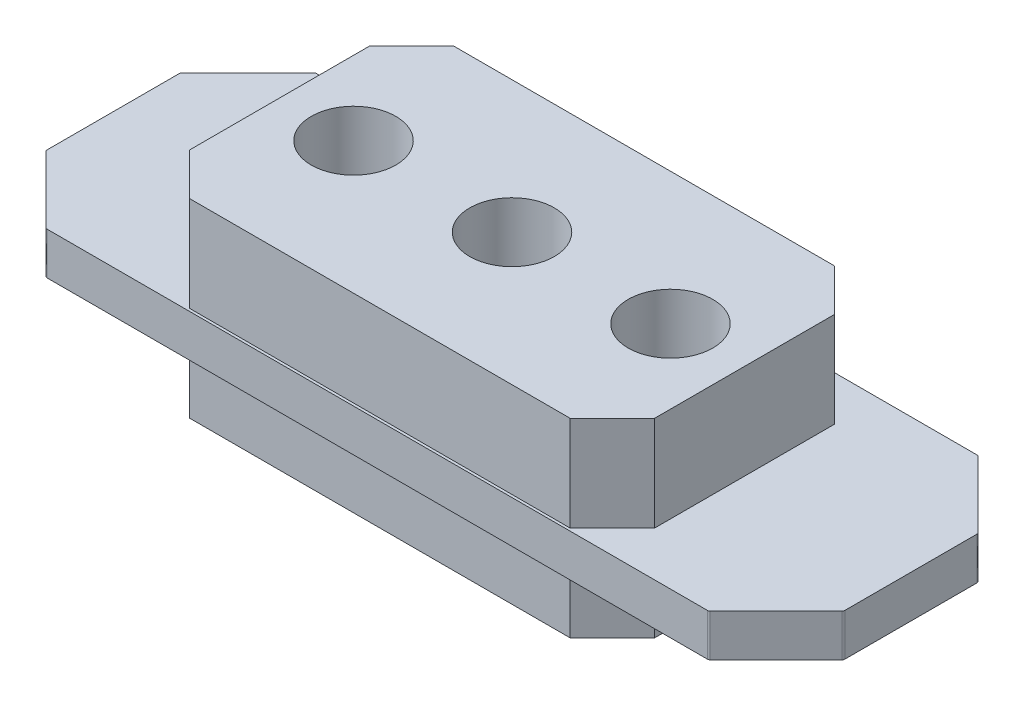
SolidWorks part; units mm, degrees
ref_plane "Front" through (0, 0, 0) normal (0, 0, 1) x (1, 0, 0)
ref_plane "Top" through (0, 0, 0) normal (0, 1, 0) x (1, 0, 0)
ref_plane "Right" through (0, 0, 0) normal (1, 0, 0) x (0, 0, -1)
sketch "Sketch1" plane through (0, 0, 0) normal (0, 1, 0) x (1, 0, 0)
  line L0 (9.5, 1.5) -> (9.5, -1.5) construction
  line L7 (10, -2) -> (14, -2) construction
  line L8 (14.5, -1.5) -> (14.5, 1.5) construction
  line L9 (14, 2) -> (10, 2) construction
  line L10 (9.5, 1.5) -> (9.5, -1.5) construction
  line L11 (10, -2) -> (14, -2) construction
  line L12 (14.5, -1.5) -> (14.5, 1.5) construction
  line L13 (14, 2) -> (10, 2) construction
  line L14 (-15.1, 2.5) -> (-15.1, -2.5)
  line L15 (-15.071, -2.571) -> (-12.571, -5.071)
  line L16 (-12.5, -5.1) -> (12.5, -5.1)
  line L17 (12.571, -5.071) -> (15.071, -2.571)
  line L18 (15.1, -2.5) -> (15.1, 2.5)
  line L19 (15.071, 2.571) -> (12.571, 5.071)
  line L20 (12.5, 5.1) -> (-12.5, 5.1)
  line L21 (-12.571, 5.071) -> (-15.071, 2.571)
  line L22 (-15.1, 2.5) -> (-15.1, -2.5)
  line L23 (-15.071, -2.571) -> (-12.571, -5.071)
  line L24 (-12.5, -5.1) -> (12.5, -5.1)
  line L25 (12.571, -5.071) -> (15.071, -2.571)
  line L26 (15.1, -2.5) -> (15.1, 2.5)
  line L27 (15.071, 2.571) -> (12.571, 5.071)
  line L28 (12.5, 5.1) -> (-12.5, 5.1)
  line L29 (-12.571, 5.071) -> (-15.071, 2.571)
  line L30 (-10, 2) -> (-14, 2) construction
  line L31 (-14.5, 1.5) -> (-14.5, -1.5) construction
  line L32 (-14, -2) -> (-10, -2) construction
  line L33 (-9.5, -1.5) -> (-9.5, 1.5) construction
  line L34 (-10, 2) -> (-14, 2) construction
  line L35 (-14.5, 1.5) -> (-14.5, -1.5) construction
  line L36 (-14, -2) -> (-10, -2) construction
  line L37 (-9.5, -1.5) -> (-9.5, 1.5) construction
  circle A0 centre (-6, 0) radius 1 construction
  circle A1 centre (6, 0) radius 1 construction
  circle A2 centre (0, 0) radius 1 construction
  circle A3 centre (-6, 0) radius 1
  circle A4 centre (6, 0) radius 1
  circle A5 centre (0, 0) radius 1
  arc A6 (9.5, -1.5) -> (10, -2) centre (10, -1.5) ccw construction
  arc A7 (14, -2) -> (14.5, -1.5) centre (14, -1.5) ccw construction
  arc A8 (-15.071, 2.571) -> (-15.1, 2.5) centre (-15.0029, 2.5018) ccw
  arc A9 (-15.1, -2.5) -> (-15.071, -2.571) centre (-15.0029, -2.5018) ccw
  arc A10 (-12.571, -5.071) -> (-12.5, -5.1) centre (-12.5018, -5.0029) ccw
  arc A11 (12.5, -5.1) -> (12.571, -5.071) centre (12.5018, -5.0029) ccw
  arc A12 (15.071, -2.571) -> (15.1, -2.5) centre (15.0029, -2.5018) ccw
  arc A13 (15.1, 2.5) -> (15.071, 2.571) centre (15.0029, 2.5018) ccw
  arc A14 (12.571, 5.071) -> (12.5, 5.1) centre (12.5018, 5.0029) ccw
  arc A15 (-12.5, 5.1) -> (-12.571, 5.071) centre (-12.5018, 5.0029) ccw
  arc A16 (-15.071, 2.571) -> (-15.1, 2.5) centre (-15.0029, 2.5018) ccw
  arc A17 (-15.1, -2.5) -> (-15.071, -2.571) centre (-15.0029, -2.5018) ccw
  arc A18 (-12.571, -5.071) -> (-12.5, -5.1) centre (-12.5018, -5.0029) ccw
  arc A19 (12.5, -5.1) -> (12.571, -5.071) centre (12.5018, -5.0029) ccw
  arc A20 (15.071, -2.571) -> (15.1, -2.5) centre (15.0029, -2.5018) ccw
  arc A21 (15.1, 2.5) -> (15.071, 2.571) centre (15.0029, 2.5018) ccw
  arc A22 (12.571, 5.071) -> (12.5, 5.1) centre (12.5018, 5.0029) ccw
  arc A23 (-12.5, 5.1) -> (-12.571, 5.071) centre (-12.5018, 5.0029) ccw
  arc A24 (14.5, 1.5) -> (14, 2) centre (14, 1.5) ccw construction
  arc A25 (10, 2) -> (9.5, 1.5) centre (10, 1.5) ccw construction
  arc A26 (9.5, -1.5) -> (10, -2) centre (10, -1.5) ccw construction
  arc A27 (14, -2) -> (14.5, -1.5) centre (14, -1.5) ccw construction
  arc A28 (14.5, 1.5) -> (14, 2) centre (14, 1.5) ccw construction
  arc A29 (10, 2) -> (9.5, 1.5) centre (10, 1.5) ccw construction
  arc A30 (-14, 2) -> (-14.5, 1.5) centre (-14, 1.5) ccw construction
  arc A31 (-14.5, -1.5) -> (-14, -2) centre (-14, -1.5) ccw construction
  arc A32 (-10, -2) -> (-9.5, -1.5) centre (-10, -1.5) ccw construction
  arc A33 (-9.5, 1.5) -> (-10, 2) centre (-10, 1.5) ccw construction
  arc A34 (-14, 2) -> (-14.5, 1.5) centre (-14, 1.5) ccw construction
  arc A35 (-14.5, -1.5) -> (-14, -2) centre (-14, -1.5) ccw construction
  arc A36 (-10, -2) -> (-9.5, -1.5) centre (-10, -1.5) ccw construction
  arc A37 (-9.5, 1.5) -> (-10, 2) centre (-10, 1.5) ccw construction
  point P0 (0, 0)
  dimension "D1" = 0
extrude "Boss-Extrude3" add sketch "Sketch1" along normal blind 1.6
sketch "Sketch3" plane through (0, 1.6, 0) normal (0, 1, 0) x (1, 0, 0)
  line L0 (-8.8, 5) -> (-8.8, -5)
  line L1 (8.8, 5) -> (8.8, -5)
  line L2 (-8.8, 5) -> (8.8, 5)
  line L3 (8.8, -5) -> (-8.8, -5)
  line L5 (7.6, 0) -> (8.8, 0) construction
  line L6 (12.5, 5.1) -> (-12.5, 5.1) construction
  circle A0 centre (-6, 0) radius 1.6
  circle A1 centre (0, 0) radius 1.6
  circle A2 centre (6, 0) radius 1.6
  point P11 (-8.8, 0)
  point P14 (8.8, 0)
  point P17 (0, 5)
  dimension "D1" = 3.2
  dimension "D3" = 0.1
  dimension "D4" = 1.2
  dimension "D5" = 10
extrude "Boss-Extrude1" add sketch "Sketch3" along normal blind 3.6 separate body
sketch "Sketch4" plane through (0, 5.2, 0) normal (0, 1, 0) x (1, 0, 0)
  circle A0 centre (6, 0) radius 1.6 construction
  circle A1 centre (-6, 0) radius 1.6 construction
  circle A2 centre (6, 0) radius 1.6
  circle A3 centre (-6, 0) radius 1.6
  circle A4 centre (-6, 0) radius 1
  circle A5 centre (6, 0) radius 1
  circle A6 centre (0, 0) radius 1.6
  circle A7 centre (0, 0) radius 1
  circle A8 centre (0, 0) radius 1.6 construction
  dimension "D1" = 2
extrude "Boss-Extrude2" add sketch "Sketch4" against normal up to surface (3.6 mm away) from offset 3 up to face at (0, 1.6, 1.6) offset against normal yes
sketch "Sketch5" plane through (0, 0, 0) normal (0, -1, 0) x (1, 0, 0)
  line L0 (-8.8, -5) -> (8.8, -5) construction
  line L1 (8.8, -5) -> (8.8, 5) construction
  line L2 (8.8, 5) -> (-8.8, 5) construction
  line L3 (-8.8, -5) -> (-8.8, 5) construction
  line L4 (-8.8, -5) -> (8.8, -5)
  line L5 (8.8, -5) -> (8.8, 5)
  line L6 (8.8, 5) -> (-8.8, 5)
  line L7 (-8.8, -5) -> (-8.8, 5)
  circle A0 centre (0, 0) radius 2
  circle A1 centre (-6, 0) radius 1
  circle A2 centre (6, 0) radius 1
  dimension "D1" = 4
  dimension "D2" = 2
extrude "Boss-Extrude4" add sketch "Sketch5" along normal blind 2 separate body
chamfer "Chamfer1" distance 1.6 angle 45 4 edges at (8.8, 3.4, -5) (8.8, 3.4, 5) (-8.8, 3.4, -5) (-8.8, 3.4, 5)
chamfer "Chamfer2" distance 1.6 angle 45 4 edges at (-8.8, -1, -5) (8.8, -1, -5) (8.8, -1, 5) (-8.8, -1, 5)
